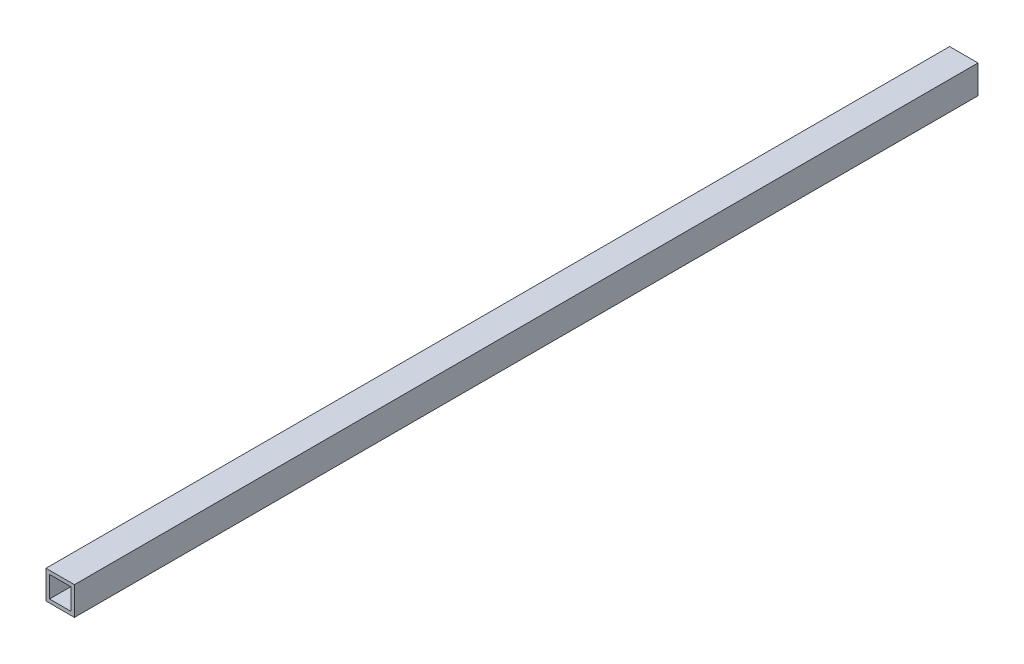
SolidWorks part; units mm, degrees
material "6061 Alloy"
ref_plane "Front Plane" through (0, 0, 0) normal (0, 0, 1) x (1, 0, 0)
ref_plane "Top Plane" through (0, 0, 0) normal (0, 1, 0) x (1, 0, 0)
ref_plane "Right Plane" through (0, 0, 0) normal (1, 0, 0) x (0, 0, -1)
sketch "Sketch1" plane through (0, 0, 0) normal (0, 0, 1) x (1, 0, 0)
  line L0 (12.7, 0) -> (9.525, 0) construction
  line L1 (-12.7, 0) -> (12.7, 0) construction
  line L2 (0, 12.7) -> (0, -12.7)
  point P7 (0, 0)
sketch "Sketch2" plane through (0, 0, 0) normal (1, 0, 0) x (0, 0, -1)
  line L0 (403.86, 0) -> (-403.86, 0)
  point P4 (0, 0)
  dimension "Length" = 807.72
sketch "Sketch3" plane through (0, 0, 0) normal (0, 0, 1) x (1, 0, 0)
  line L0 (-12.7, 0) -> (12.7, 0) construction
  line L5 (12.7, -12.7) -> (-12.7, -12.7)
  line L6 (12.7, -12.7) -> (12.7, 12.7)
  line L11 (12.7, 12.7) -> (-12.7, 12.7)
  line L12 (-12.7, -12.7) -> (-12.7, 12.7)
  line L14 (12.7, -12.7) -> (-12.7, 12.7) construction
  line L15 (12.7, 12.7) -> (-12.7, -12.7) construction
  line L16 (9.525, -9.525) -> (-9.525, -9.525)
  line L17 (9.525, -9.525) -> (9.525, 9.525)
  line L18 (9.525, 9.525) -> (-9.525, 9.525)
  line L19 (-9.525, -9.525) -> (-9.525, 9.525)
  line L20 (9.525, -9.525) -> (-9.525, 9.525) construction
  line L21 (9.525, 9.525) -> (-9.525, -9.525) construction
  point P0 (0, 0)
  point P5 (0, 0)
  point P13 (9.525, -12.7)
  dimension "D1" = 3.175
extrude "Boss-Extrude1" add sketch "Sketch3" along normal up to vertex (403.86 mm away) and the other way up to vertex (403.86 mm away) up to point (0, 0, 403.86) other way up to point (0, 0, -403.86)
sketch "Sketch5" plane through (0, 0, 0) normal (1, 0, 0) x (0, 0, -1)
  line L0 (-403.86, 0) -> (403.86, 0) construction
  line L3 (-403.86, -12.7) -> (-403.86, 12.7) construction
  line L4 (403.86, -12.7) -> (403.86, 12.7) construction
  point P6 (-375.285, 0)
  point P7 (-365.76, 0)
  point P8 (365.76, 0)
  point P10 (375.285, 0)
  dimension "D1" = 28.575
  dimension "D2" = 38.1
  dimension "D3" = 28.575
  dimension "D4" = 38.1
equation "\"D1@Sketch3\"=\"Wall thickness@Sketch1\""
equation "\"D1@Sketch5\"=\"Width@Sketch1\"*1.125"
equation "\"D2@Sketch5\"=\"Width@Sketch1\"*1.5"
equation "\"D3@Sketch5\"=\"D1@Sketch5\""
equation "\"D4@Sketch5\"=\"D2@Sketch5\""
equation "\"D2@Sketch3\"=\"Wall Thickness@Sketch1\""
